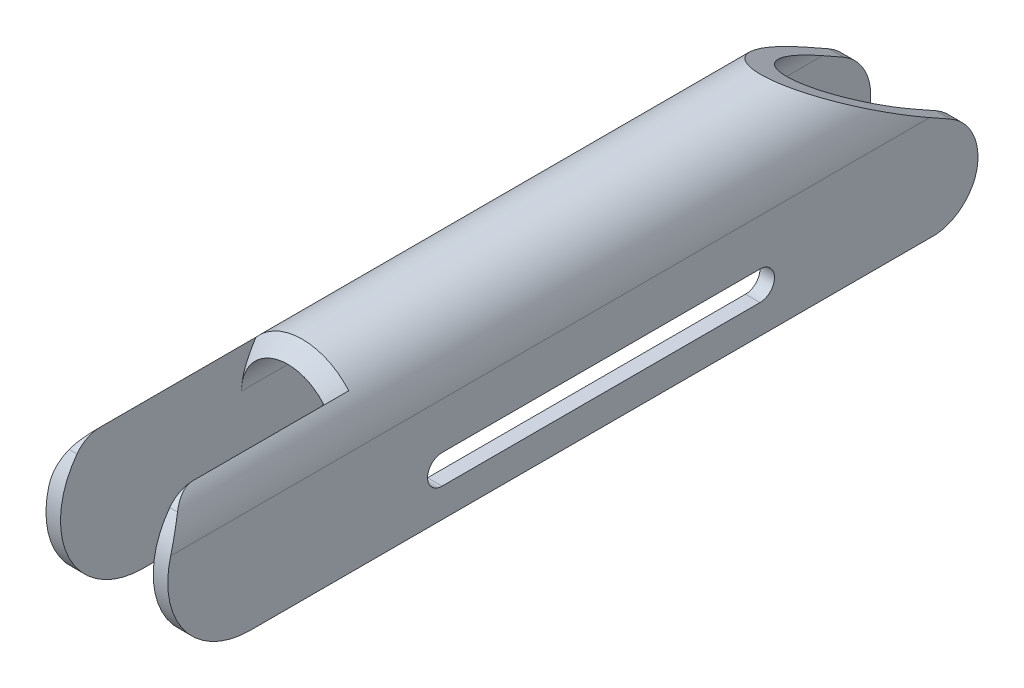
SolidWorks part; units mm, degrees
ref_plane "Front Plane" through (0, 0, 0) normal (0, 0, 1) x (1, 0, 0)
ref_plane "Top Plane" through (0, 0, 0) normal (0, 1, 0) x (1, 0, 0)
ref_plane "Right Plane" through (0, 0, 0) normal (1, 0, 0) x (0, 0, -1)
sketch "Sketch1" plane through (0, 0, 0) normal (0, 0, 1) x (1, 0, 0)
  line L0 (0, 0) -> (0, -36)
  line L2 (42, 0) -> (42, -36)
  line L3 (42, -36) -> (0, -36)
  arc A0 (0, 0) -> (42, 0) centre (21, 0) cw
  dimension "D1" = 36
  dimension "D2" = 42
extrude "WholeBody" add sketch "Sketch1" against normal blind 280
sketch "Sketch2" plane through (42, 0, 0) normal (1, 0, 0) x (0, 0, -1)
  line L0 (280, 21) -> (0, 21) construction
  line L1 (280, 21) -> (0, 21)
  line L2 (0, -36) -> (0, 0) construction
  line L3 (0, 21) -> (0, 0) construction
  line L4 (0, -36) -> (0, 0)
  line L5 (0, 21) -> (0, 0)
  line L6 (280, -36) -> (0, -36) construction
  line L7 (280, -36) -> (0, -36)
  line L9 (29, 21) -> (29, -36)
  arc A2 (29, 21) -> (29, -36) centre (29, -7.5) ccw
  line M4 (0, -36) -> (280, -36)
  line M6 (280, 0) -> (0, 0)
  dimension "D1" = 29
extrude "UpperCurve" cut sketch "Sketch2" against normal through all contours A2 L1 L5 M6 | A2 L4 M4 region at (42, 14.6216, -6.5679) region at (42, -28.2036, -6.177)
sketch "Sketch6" plane through (0, 0, -280) normal (0, 0, -1) x (-1, 0, 0)
  line L0 (-37, 0) -> (-37, -31)
  line L2 (-5, -31) -> (-5, 0)
  line L3 (-42, 0) -> (-42, -36)
  line L4 (-42, -36) -> (0, -36)
  line L5 (0, -36) -> (0, 0)
  line L6 (-42, 0) -> (-42, -36)
  line L7 (-42, -36) -> (0, -36)
  line L8 (0, -36) -> (0, 0)
  line L9 (-37, -31) -> (-5, -31) construction
  line L10 (-37, -31) -> (-37, -36)
  line L12 (-5, -31) -> (-5, -36)
  arc A0 (-5, 0) -> (-37, 0) centre (-21, 0) ccw
  arc A1 (0, 0) -> (-42, 0) centre (-21, 0) ccw
  arc A2 (0, 0) -> (-42, 0) centre (-21, 0) ccw
  dimension "D1" = 0
  dimension "D2" = 5
extrude "Cut-Extrude5" cut sketch "Sketch6" against normal through all contours L0 L9 L2 A0 | L9 L10 L7 L12 region at (21, -9.0705, -280) region at (21, -33.5, -280)
sketch "Sketch8" plane through (0, 0, 0) normal (-1, 0, 0) x (0, 0, 1)
  line L0 (-29, 21) -> (-280, 21) construction
  line L1 (-29, 21) -> (-280, 21)
  line L2 (-226.0825, 21) -> (-226.0825, -36)
  line L9 (-226.0825, -36) -> (-265.553, -36)
  line L10 (-280, -36) -> (-29, -36) construction
  line L11 (-280, -36) -> (-29, -36)
  line L14 (-226.0825, 21) -> (-270.5651, -4.0542)
  line L16 (-280, 0) -> (-280, -36) construction
  line L17 (-280, 21) -> (-280, 0) construction
  line L18 (-280, 0) -> (-280, -36)
  line L19 (-280, 21) -> (-280, 0)
  arc A2 (-270.5651, -4.0542) -> (-280, -20.1968) centre (-261.473, -20.1968) ccw
  arc A3 (-280, -20.1968) -> (-265.553, -36) centre (-264.1331, -20.1968) ccw
  line M5 (-280, -36) -> (-29, -36)
  line M7 (-1.5045, 0) -> (-280, 0)
  line M8 (-280, 0) -> (-280, -36)
  dimension "D1" = 18.527
  dimension "D2" = 15.8669
  dimension "D3" = 9.4349
  dimension "D4" = 14.447
extrude "Cut-Extrude6" cut sketch "Sketch8" against normal through all contours L1 L19 L14 M7 | A2 L14 M7 M8 | A3 L18 M5 region at (0, 12.3497, -260.7204) region at (0, -4.5784, -275.1562) region at (0, -32.4567, -276.526)
sketch "Sketch9" plane through (0, -36, 0) normal (0, -1, 0) x (1, 0, 0)
  line L1 (21.1153, -57.9421) -> (21.1153, -13.9694) construction
  line L2 (5, -1.5045) -> (5, -263.3671) construction
  line L3 (5, -0.5) -> (5, -57.9421)
  line L4 (37, -0.5) -> (37, -29) construction
  line L5 (37, -29) -> (37, -265.553) construction
  line L6 (37, 4.098) -> (37, -29)
  line L7 (37, -29) -> (37, -57.9421)
  line L8 (37, 4.098) -> (5, 4.098)
  line L9 (5, -57.9421) -> (37, -57.9421)
  line L10 (5, 4.098) -> (5, -0.5)
  line L11 (0, -29) -> (5, -29) construction
  point P15 (0, 0)
  point P16 (5, -0.5)
  point P17 (0, 0)
  point P18 (5, -0.5)
  point P19 (5, -0.5496)
  dimension "D1" = 33.098
  dimension "D2" = 28.9421
extrude "UpperHole" cut sketch "Sketch9" against normal through all
chamfer "Chamfer1" distance 10 angle 45 1 edges at (21, 21, -57.9421)
sketch "Sketch11" plane through (0, 0, 0) normal (-1, 0, 0) x (0, 0, 1)
  line L0 (-67.9421, 13.6015) -> (-9.8433, 13.6015) construction
  line L1 (-67.9421, 13.6015) -> (-14.2011, 13.6015)
  line L2 (-67.9421, 13.6015) -> (-9.8433, 13.6015)
  arc A0 (-1.5045, 0) -> (-9.8433, 13.6015) centre (-29, -7.5) ccw construction
  arc A1 (-1.5045, 0) -> (-6.2017, 9.6023) centre (-29, -7.5) ccw
  arc A2 (-6.2017, 9.6023) -> (-14.2011, 13.6015) centre (-14.2011, 3.6015) ccw
  arc A3 (-29, -36) -> (-9.8433, 13.6015) centre (-29, -7.5) ccw construction
  arc A4 (-29, -36) -> (-9.8433, 13.6015) centre (-29, -7.5) ccw
  dimension "D1" = 10
extrude "Cut-Extrude8" cut sketch "Sketch11" against normal through all contours A2 A4 L2 region at (0, 12.8133, -9.8953)
sketch "Sketch12" plane through (0, 0, 0) normal (-1, 0, 0) x (0, 0, 1)
  line L0 (-204.781, -20.9701) -> (-95.1409, -20.9701) construction
  line L1 (-204.781, -15.9579) -> (-95.1409, -15.9579)
  line L2 (-204.781, -25.9822) -> (-95.1409, -25.9822)
  line L3 (-265.553, -36) -> (-29, -36) construction
  arc A0 (-204.781, -15.9579) -> (-204.781, -25.9822) centre (-204.781, -20.9701) ccw
  arc A1 (-95.1409, -25.9822) -> (-95.1409, -15.9579) centre (-95.1409, -20.9701) ccw
  point P2 (-149.961, -20.9701)
  dimension "D1" = 5.0121
  dimension "D2" = 66.1409
  dimension "D3" = 120.961
  dimension "D4" = 15.0299
extrude "Cut-Extrude9" cut sketch "Sketch12" against normal through all contours L2 A1 L1 A0
